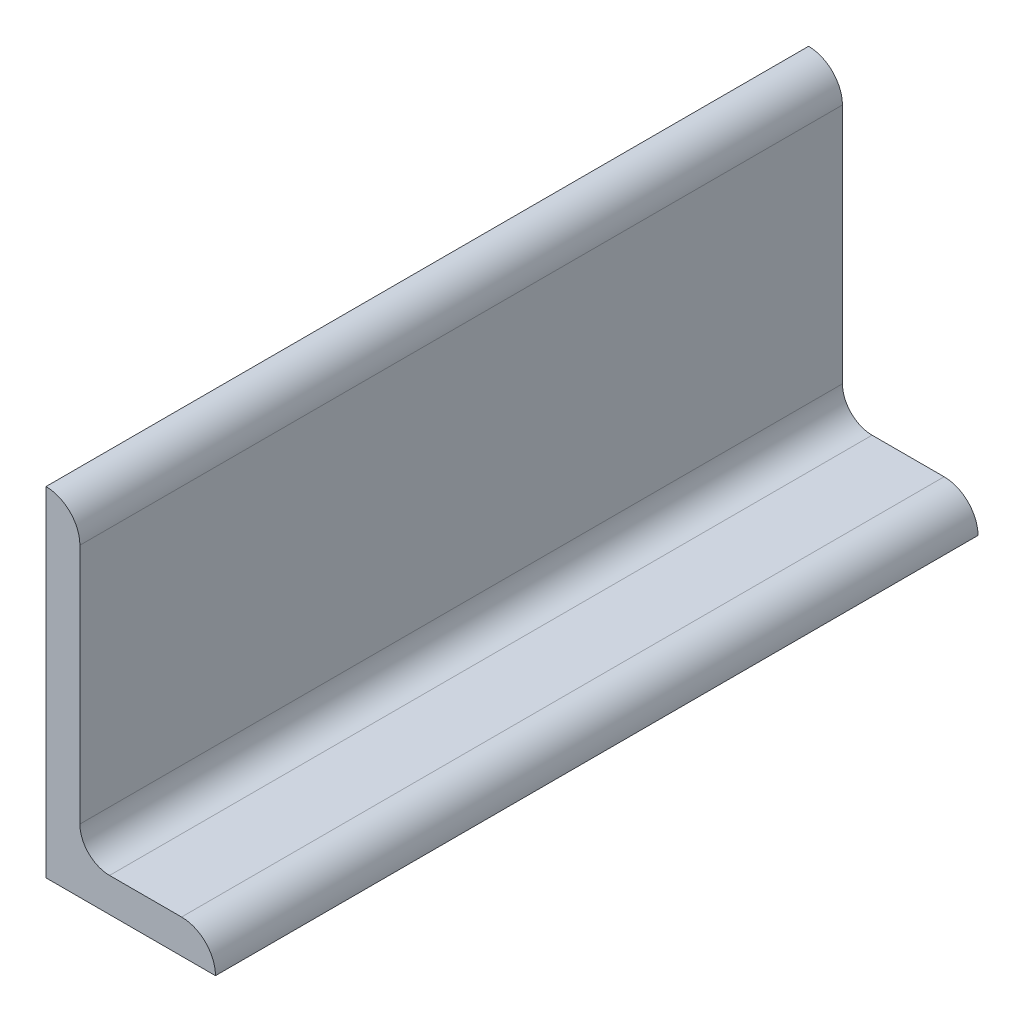
SolidWorks part; units mm, degrees
ref_plane "Plane1" through (0, 0, 0) normal (0, 0, 1) x (1, 0, 0)
ref_plane "Plane2" through (0, 0, 0) normal (0, 1, 0) x (1, 0, 0)
ref_plane "Plane3" through (0, 0, 0) normal (1, 0, 0) x (0, 0, -1)
sketch "Sketch1" plane through (0, 0, 0) normal (0, 0, 1) x (1, 0, 0)
  line L0 (0, 80) -> (0, 0)
  line L1 (0, 80) -> (9.525, 80) construction
  line L2 (8, 80) -> (8, 15)
  line L3 (15, 8) -> (40, 8)
  line L4 (40, 9.525) -> (40, 0) construction
  line L5 (40, 0) -> (0, 0)
  line L6 (40, 8) -> (40, 0)
  line L7 (0, 80) -> (8, 80)
  arc A2 (15, 8) -> (8, 15) centre (15, 15) cw
  dimension "Radius_1" = 7
  dimension "V_leg" = 80
  dimension "H_leg" = 40
extrude "BaseSteelAngle" add sketch "Sketch1" along normal mid plane 180
fillet "ToeFillet" radius 8 2 edges at (40, 8, 0) (8, 80, 0)
